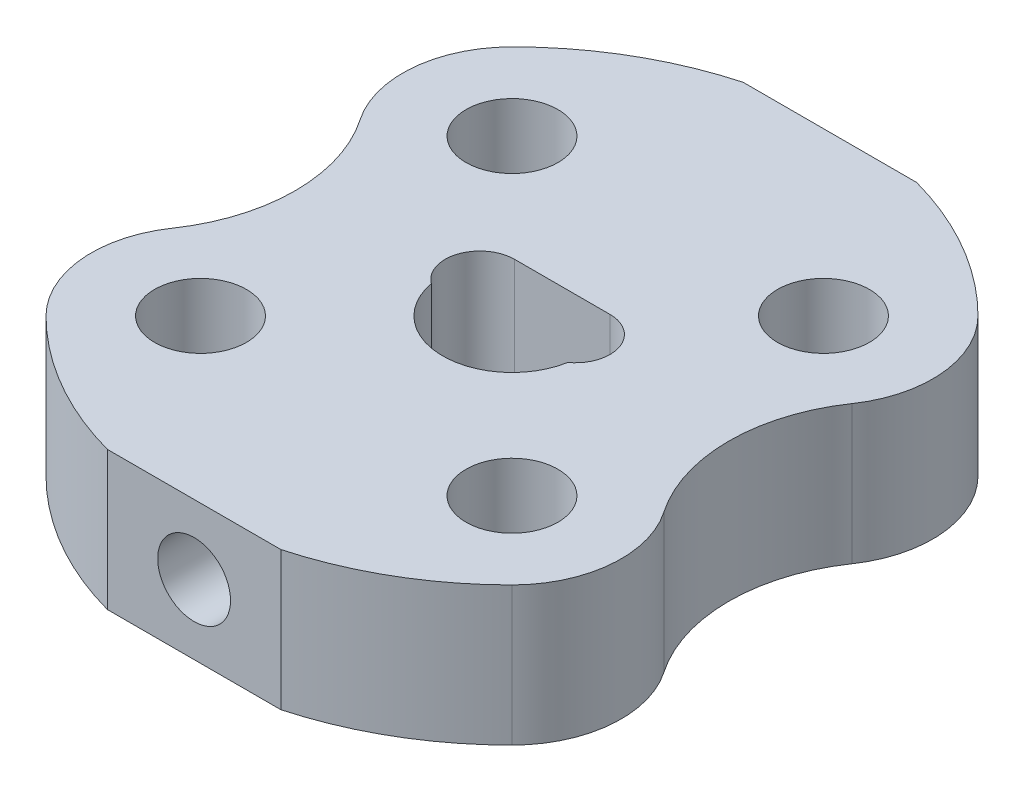
SolidWorks part; units mm, degrees
ref_plane "Front Plane" through (0, 0, 0) normal (0, 0, 1) x (1, 0, 0)
ref_plane "Top Plane" through (0, 0, 0) normal (0, 1, 0) x (1, 0, 0)
ref_plane "Right Plane" through (0, 0, 0) normal (1, 0, 0) x (0, 0, -1)
sketch "Sketch1" plane through (0, 0, 0) normal (0, 1, 0) x (1, 0, 0)
  line L0 (-9.5, 0) -> (9.5, 0) construction
  line L1 (0, 9.5) -> (0, -9.5) construction
  line L2 (0, 0) -> (6.7175, 6.7175) construction
  line L3 (-1.3775, 1.45) -> (1.3775, 1.45)
  line L4 (-1.3775, 1.45) -> (-1.3775, 0) construction
  line L5 (-2.5, -9.1652) -> (2.5, -9.1652)
  line L6 (-2.5, 9.1652) -> (2.5, 9.1652)
  line L7 (-6.25, 0) -> (-6.25, -1.8776) construction
  circle A0 centre (0, 0) radius 9.5
  circle A1 centre (0, 0) radius 2
  circle A2 centre (4.4901, 4.4901) radius 1.325
  circle A3 centre (-4.4901, 4.4901) radius 1.325
  circle A4 centre (4.4901, -4.4901) radius 1.325
  circle A5 centre (-4.4901, -4.4901) radius 1.325
  circle A6 centre (-1.3775, 0.45) radius 1
  circle A7 centre (1.3775, 0.45) radius 1
  circle A8 centre (-7.5, 0) radius 1.25
  circle A9 centre (-4.4901, 4.4901) radius 3.15
  circle A10 centre (-4.4901, -4.4901) radius 3.15
  arc A11 (-7.0891, -2.7103) -> (-7.0891, 2.7103) centre (-11.0466, 0) ccw
  arc A12 (7.0891, -2.7103) -> (7.0891, 2.7103) centre (11.0466, 0) cw
  circle A13 centre (4.4901, -4.4901) radius 3.15
  circle A14 centre (4.4901, 4.4901) radius 3.15
  point P19 (0, -2)
  point P38 (-6.25, 0)
  dimension "D1" = 19
  dimension "D2" = 4
  dimension "D3" = 2.65
  dimension "D7" = 2
  dimension "D9" = 2.5
  dimension "D4" = 6.35
  dimension "D5" = 45
  dimension "D6" = 3.45
  dimension "D8" = 5
  dimension "D10" = 15
extrude "Base shape" add sketch "Sketch1" along normal blind 4 contours A12 A14 A0 L6 A9 A11 A10 L5 A13 A1 A7 A6 | A9 A3 | A14 A2 | A13 A4 | A10 A5 | L3 A1 region at (0, 0, -1.6728) region at (-4.6522, 0, 8.0161) region at (-7.538, 0, 4.7727) region at (1.4423, 0, 4.2075) region at (-3.3188, 0, -7.318) region at (7.318, 0, -5.6615)
sketch "Sketch3" plane through (0, 0, 9.1652) normal (0, 0, 1) x (1, 0, 0)
  line L0 (-2.5, 4) -> (2.5, 0) construction
  circle A0 centre (0, 2) radius 1.05
  point P2 (0, 2)
  dimension "D1" = 2.1
extrude "M2.5 Grub screw cut" cut sketch "Sketch3" against normal up to next
sketch "Sketch6" plane through (0, 0, -9.1652) normal (0, 0, -1) x (-1, 0, 0)
  line L0 (-2.5, 4) -> (2.5, 0) construction
  circle A0 centre (0, 2) radius 1.25
  dimension "D1" = 2.5
extrude "Grub opposite cut" [suppressed] cut sketch "Sketch6" against normal up to next
sketch "Sketch5" plane through (0, 4, 0) normal (0, 1, 0) x (1, 0, 0)
  line L0 (-2.5, -9.1652) -> (2.5, -9.1652) construction
  line L1 (-7.6401, 9.1652) -> (7.6401, 9.1652)
  line L2 (-7.6401, 9.1652) -> (-7.6401, -9.1652)
  line L3 (-7.6401, -9.1652) -> (7.6401, -9.1652)
  line L4 (7.6401, 9.1652) -> (7.6401, -9.1652)
  line L5 (-7.6401, 9.1652) -> (7.6401, -9.1652) construction
  line L6 (-7.6401, -9.1652) -> (7.6401, 9.1652) construction
  arc A0 (-6.7175, 6.7175) -> (-7.0891, 2.7103) centre (-4.4901, 4.4901) ccw construction
  point P0 (0, 0)
  point P9 (0, 0)
  point P10 (7.6401, -9.1652)
